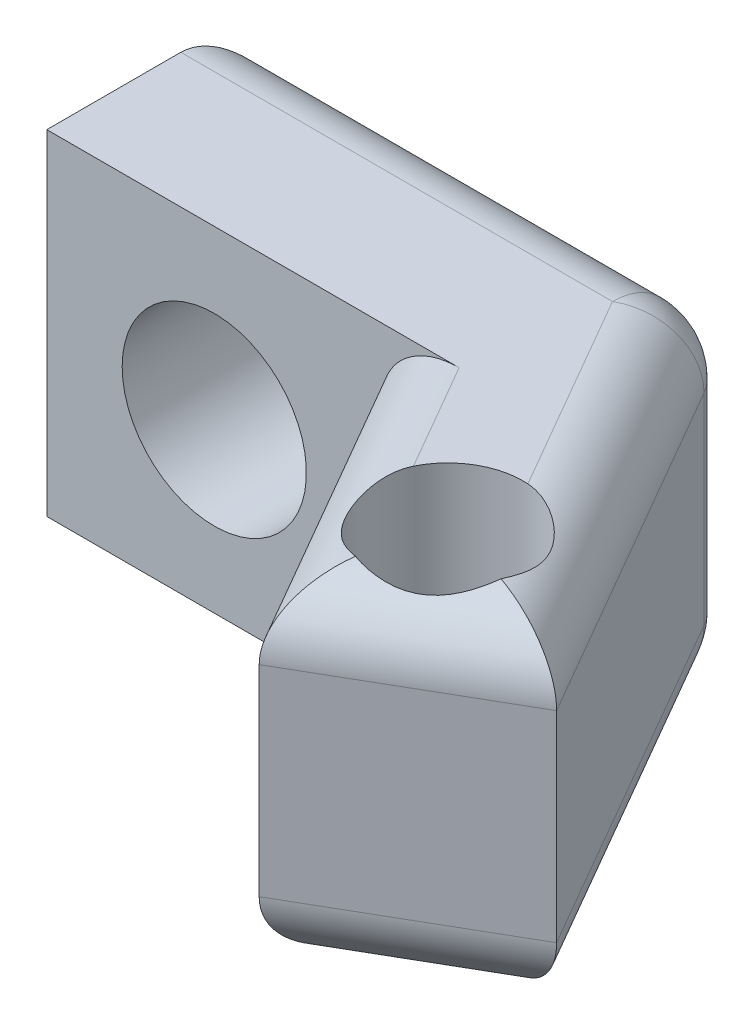
SolidWorks part; units mm, degrees
ref_plane "Спереди" through (0, 0, 0) normal (0, 0, 1) x (1, 0, 0)
ref_plane "Сверху" through (0, 0, 0) normal (0, 1, 0) x (1, 0, 0)
ref_plane "Справа" through (0, 0, 0) normal (1, 0, 0) x (0, 0, -1)
sketch "Эскиз1" plane through (0, 0, 0) normal (0, 1, 0) x (1, 0, 0)
  line L0 (-22.1053, 3.5877) -> (-22.1053, -2.4123)
  line L1 (-22.1053, -2.4123) -> (-12.1053, -2.4123)
  line L2 (-12.1053, -2.4123) -> (-7.1053, -11.0725)
  line L3 (-7.1053, -11.0725) -> (-1.4761, -7.8225)
  line L4 (-1.4761, -7.8225) -> (-8.0638, 3.5877)
  line L5 (-8.0638, 3.5877) -> (-22.1053, 3.5877)
  dimension "D1" = 6
  dimension "D2" = 10
  dimension "D3" = 10
  dimension "D4" = 120
  dimension "D5" = 6.5
extrude "Бобышка-Вытянуть1" add sketch "Эскиз1" along normal blind 10
sketch "Эскиз2" plane through (0, 0, -3.5877) normal (0, 0, -1) x (-1, 0, 0)
  line L1 (8.0638, 10) -> (22.1053, 10) construction
  line L2 (22.1053, 10) -> (22.1053, 0) construction
  circle A0 centre (17.1053, 5) radius 2.75
  point P2 (16.5554, 5.0472)
  dimension "D1" = 5.5
  dimension "D2" = 5
  dimension "D3" = 5
extrude "Вырез-Вытянуть1" cut sketch "Эскиз2" against normal through all and the other way through all
sketch "Эскиз3" plane through (0, 0, 0) normal (0, -1, 0) x (1, 0, 0)
  line L0 (-1.4761, 7.8225) -> (-8.0638, -3.5877) construction
  line L1 (-7.1053, 11.0725) -> (-1.4761, 7.8225) construction
  circle A0 centre (-5.9157, 6.633) radius 2.25
  point P2 (-6.0215, 7.1803)
  dimension "D1" = 4.5
  dimension "D2" = 3.25
  dimension "D3" = 3.25
extrude "Вырез-Вытянуть2" cut sketch "Эскиз3" against normal through all
fillet "Скругление1" radius 2 10 edges at (-22.1053, 5, -3.5877) (-4.2907, 10, 9.4475) (-4.2907, 0, 9.4475) (-9.6053, 0, 6.7424) (-9.6053, 10, 6.7424) (-4.77, 10, 2.1174) (-4.77, 0, 2.1174) (-15.0845, 10, -3.5877) (-15.0845, 0, -3.5877) (-8.0638, 5, -3.5877)
